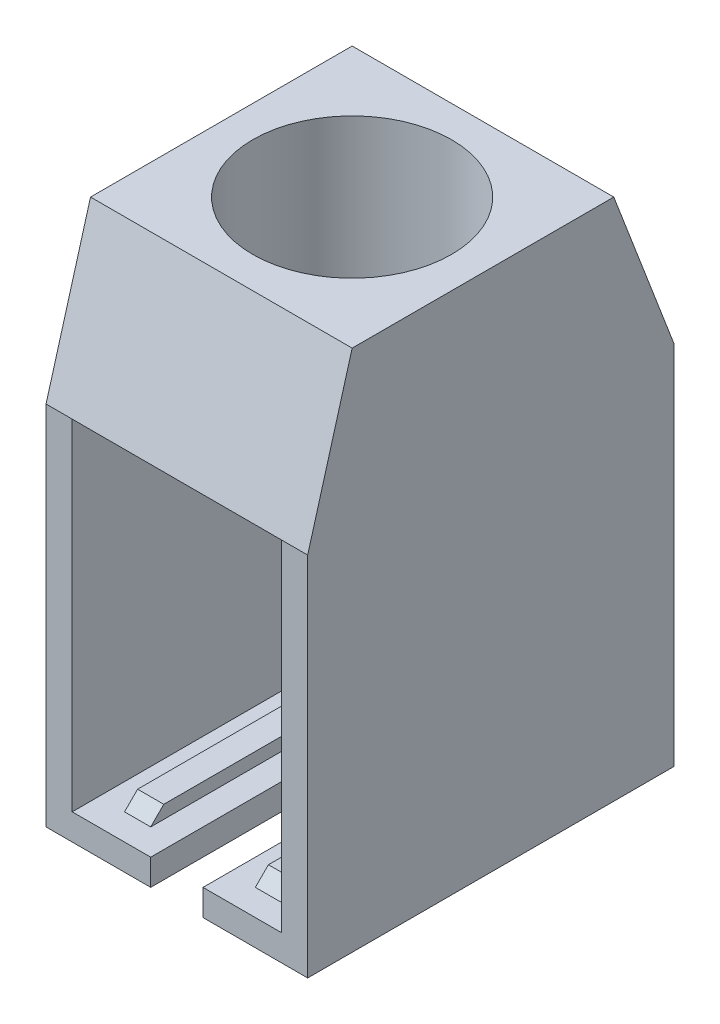
SolidWorks part; units mm, degrees
material "PVC 0.007 Plasticized"
ref_plane "Front Plane" through (0, 0, 0) normal (0, 0, 1) x (1, 0, 0)
ref_plane "Top Plane" through (0, 0, 0) normal (0, 1, 0) x (1, 0, 0)
ref_plane "Right Plane" through (0, 0, 0) normal (1, 0, 0) x (0, 0, -1)
sketch "Sketch1" plane through (0, 0, 0) normal (0, 1, 0) x (1, 0, 0)
  line L1 (2.5, 3.5) -> (-2.5, 3.5)
  line L2 (2.5, 3.5) -> (2.5, -3.5)
  line L3 (2.5, -3.5) -> (-2.5, -3.5)
  line L4 (-2.5, 3.5) -> (-2.5, -3.5)
  line L5 (2.5, 3.5) -> (-2.5, -3.5) construction
  line L6 (2.5, -3.5) -> (-2.5, 3.5) construction
  point P0 (0, 0)
  dimension "D1" = 5
  dimension "D2" = 7
extrude "Boss-Extrude1" add sketch "Sketch1" along normal blind 10
sketch "Sketch2" plane through (2.5, 0, 0) normal (1, 0, 0) x (0, 0, -1)
  line L0 (-3.5, 7) -> (-2.65, 10)
  line L1 (-3.5, 10) -> (-3.5, 0) construction
  line L2 (-3.5, 10) -> (3.5, 10) construction
  line L3 (-2.65, 10) -> (-3.5, 10)
  line L4 (-3.5, 10) -> (-3.5, 7)
  line L5 (2.35, 10) -> (3.5, 10)
  line L6 (3.5, 10) -> (3.5, 7)
  line L7 (3.5, 10) -> (3.5, 0) construction
  line L8 (3.5, 7) -> (2.35, 10)
  line L9 (-0.15, 10) -> (-0.15, 0) construction
  line L10 (-3.5, 0) -> (3.5, 0) construction
  line L11 (-2.65, 10) -> (2.35, 10) construction
  point P11 (-0.15, 10)
  dimension "D1" = 7
  dimension "D2" = 5
  dimension "D3" = 3.35
extrude "Cut-Extrude1" cut sketch "Sketch2" against normal through all
sketch "Sketch3" plane through (0, 0, 3.5) normal (0, 0, 1) x (1, 0, 0)
  line L0 (2.5, 7) -> (2.5, 0) construction
  line L1 (-2, 6.5) -> (2, 6.5)
  line L2 (-2, 6.5) -> (-2, 0.5)
  line L3 (-2, 0.5) -> (2, 0.5)
  line L4 (2, 6.5) -> (2, 0.5)
  line L5 (-2, 6.5) -> (2, 0.5) construction
  line L6 (-2, 0.5) -> (2, 6.5) construction
  line L7 (-2.5, 0) -> (2.5, 0) construction
  line L9 (-2.5, 7) -> (2.5, 7) construction
  point P0 (0, 3.5)
  dimension "D1" = 0.5
  dimension "D2" = 0.5
  dimension "D3" = 0.5
extrude "Cut-Extrude2" cut sketch "Sketch3" against normal offset from surface (6.5 mm away) 0.5 up to face at (0, 3.5, -3.5)
sketch "Sketch4" plane through (0, 10, 0) normal (0, 1, 0) x (1, 0, 0)
  circle A0 centre (0, -0.15) radius 1.9
  point P2 (2.5, -0.15)
  dimension "D1" = 3.8
extrude "Cut-Extrude3" cut sketch "Sketch4" against normal up to next
sketch "Sketch5" plane through (0, 0, 0) normal (0, -1, 0) x (1, 0, 0)
  line L0 (-0.5, 3.5) -> (-0.5, 0.15)
  line L1 (-2.5, 3.5) -> (2.5, 3.5) construction
  line L2 (0.5, 0.15) -> (0.5, 3.5)
  line L3 (0.5, 3.5) -> (-0.5, 3.5)
  circle A0 centre (0, 0.15) radius 1.9 construction
  circle A1 centre (0, 0.15) radius 1.9 construction
  arc A2 (-0.5, 0.15) -> (0.5, 0.15) centre (0, 0.15) ccw
  point P10 (0, 3.5)
  dimension "D1" = 1
extrude "Cut-Extrude4" cut sketch "Sketch5" against normal up to next
sketch "Sketch6" plane through (0, 0.5, 0) normal (0, 1, 0) x (1, 0, 0)
  line L0 (-2, 0) -> (-1.25, 0)
  line L1 (-1.5, 3) -> (-1, 3)
  line L2 (-1.5, 3) -> (-1.5, -3)
  line L3 (-1.5, -3) -> (-1, -3)
  line L4 (-1, 3) -> (-1, -3)
  line L5 (-1.5, 3) -> (-1, -3) construction
  line L6 (-1.5, -3) -> (-1, 3) construction
  line L7 (1, 3) -> (1.5, 3)
  line L8 (1, 3) -> (1, -3)
  line L9 (1, -3) -> (1.5, -3)
  line L10 (1.5, 3) -> (1.5, -3)
  line L11 (1, 3) -> (1.5, -3) construction
  line L12 (1, -3) -> (1.5, 3) construction
  line L13 (-1.25, 0) -> (-1, 0)
  line L14 (1.25, 0) -> (2, 0)
  line L19 (0.5, -0.15) -> (0.5, -3.5)
  line L20 (0.5, -3.5) -> (2, -3.5)
  line L21 (2, -3.5) -> (2, 3)
  line L22 (2, 3) -> (-2, 3)
  line L23 (-2, 3) -> (-2, -3.5)
  line L24 (-2, -3.5) -> (-0.5, -3.5)
  line L25 (-0.5, -3.5) -> (-0.5, -0.15)
  line L26 (0.5, -0.15) -> (0.5, -3.5) construction
  line L27 (0.5, -3.5) -> (2, -3.5) construction
  line L28 (2, -3.5) -> (2, 3) construction
  line L29 (2, 3) -> (-2, 3) construction
  line L30 (-2, 3) -> (-2, -3.5) construction
  line L31 (-2, -3.5) -> (-0.5, -3.5) construction
  line L32 (-0.5, -3.5) -> (-0.5, -0.15) construction
  arc A1 (0.5, -0.15) -> (-0.5, -0.15) centre (0, -0.15) ccw
  arc A2 (0.5, -0.15) -> (-0.5, -0.15) centre (0, -0.15) ccw construction
  point P0 (-1.25, 0)
  point P5 (1.25, 0)
  point P26 (-1.25, -3)
  point P27 (-1.25, -3.5)
  point P29 (1.25, -3.5)
  line M21 (2, 3) -> (-2, 3)
  dimension "D1" = 0
  dimension "D2" = 0.5
extrude "Boss-Extrude3" add sketch "Sketch6" along normal blind 0.25 contours L0 L13 L4 L2 M21 | L13 L0 L2 L3 L4 | L10 L8 L9 M21 region at (-1.25, 0.5, -1.5) region at (-1.25, 0.5, 1.5) region at (1.25, 0.5, -2.9398)
chamfer "Chamfer1" distance 0.25 angle 45 2 edges at (1.25, 0.75, 3) (-1.25, 0.75, 3)
chamfer "Chamfer2" distance 0.5 angle 45 1 edges at (0, 6.5, 3.5)
equation "\"Pin Spacing\"= 5mm"
equation "\"Connector Height\"= 10mm"
equation "\"Connector Depth\"= 7mm"
equation "\"Connector Width\"= \"Pin Spacing\""
equation "\"D1@Sketch1\"=\"Connector Width\""
equation "\"D2@Sketch1\"=\"Connector Depth\""
equation "\"D1@Boss-Extrude1\"=\"Connector Height\""
equation "\"Set Screw Diameter\"= 3.5mm"
equation "\"D1@Sketch4\"=\"Set Screw Diameter\" +.3"
equation "\"Pin Width\"= .9mm"
